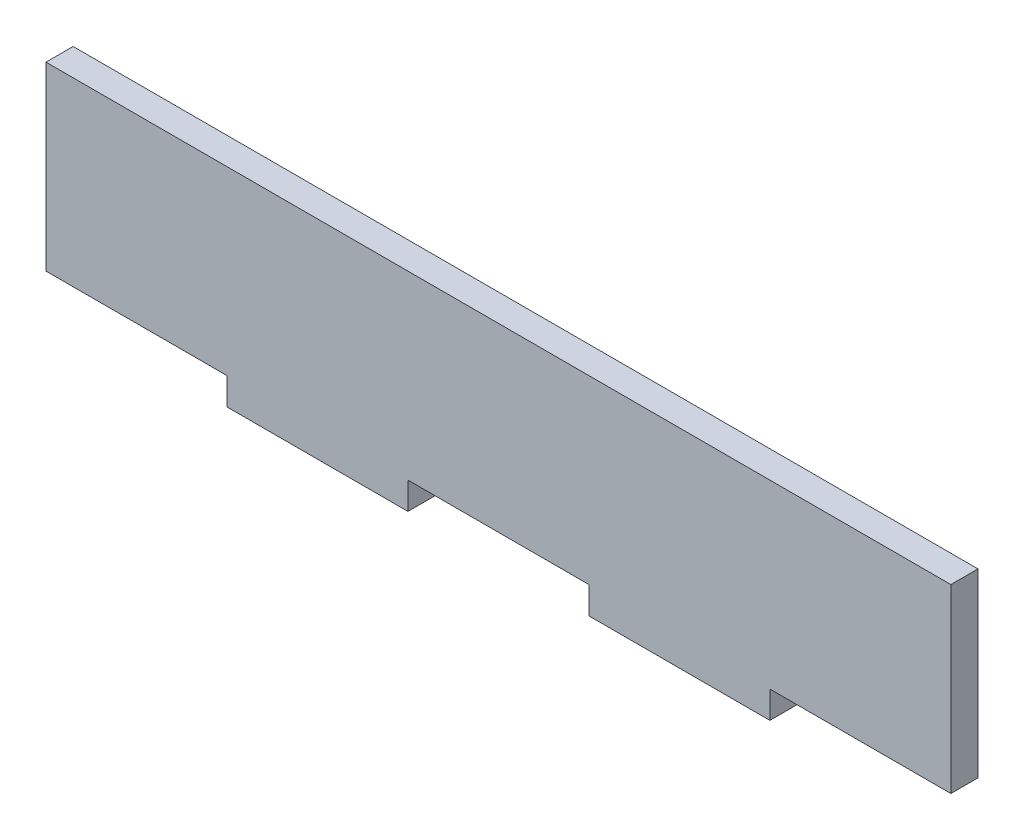
SolidWorks part; units mm, degrees
material "Pine"
ref_plane "Front Plane" through (0, 0, 0) normal (0, 0, 1) x (1, 0, 0)
ref_plane "Top Plane" through (0, 0, 0) normal (0, 1, 0) x (1, 0, 0)
ref_plane "Right Plane" through (0, 0, 0) normal (1, 0, 0) x (0, 0, -1)
sketch "Sketch1" plane through (0, 0, 0) normal (0, 0, 1) x (1, 0, 0)
  line L1 (-100, 23) -> (100, 23)
  line L2 (-100, 23) -> (-100, -23)
  line L3 (-100, -23) -> (100, -23)
  line L4 (100, 23) -> (100, -23)
  line L5 (-100, 23) -> (100, -23) construction
  line L6 (-100, -23) -> (100, 23) construction
  point P0 (0, 0)
  dimension "D1" = 46
  dimension "D2" = 200
extrude "Boss-Extrude1" add sketch "Sketch1" along normal blind 6
sketch "Sketch2" plane through (0, 0, 6) normal (0, 0, 1) x (1, 0, 0)
  line L0 (-20, -23) -> (-20, -17)
  line L1 (-100, -23) -> (-60, -23)
  line L2 (-100, -23) -> (-100, -17)
  line L3 (-100, -17) -> (-60, -17)
  line L4 (-60, -23) -> (-60, -17)
  line L5 (-20, -23) -> (20, -23)
  line L6 (20, -23) -> (20, -17)
  line L7 (-20, -17) -> (20, -17)
  line L8 (60, -23) -> (60, -17)
  line L9 (60, -23) -> (100, -23)
  line L10 (100, -23) -> (100, -17)
  line L11 (60, -17) -> (100, -17)
  dimension "D1" = 40
  dimension "D2" = 6
  dimension "D3" = 3
extrude "Cut-Extrude1" cut sketch "Sketch2" against normal blind 6
